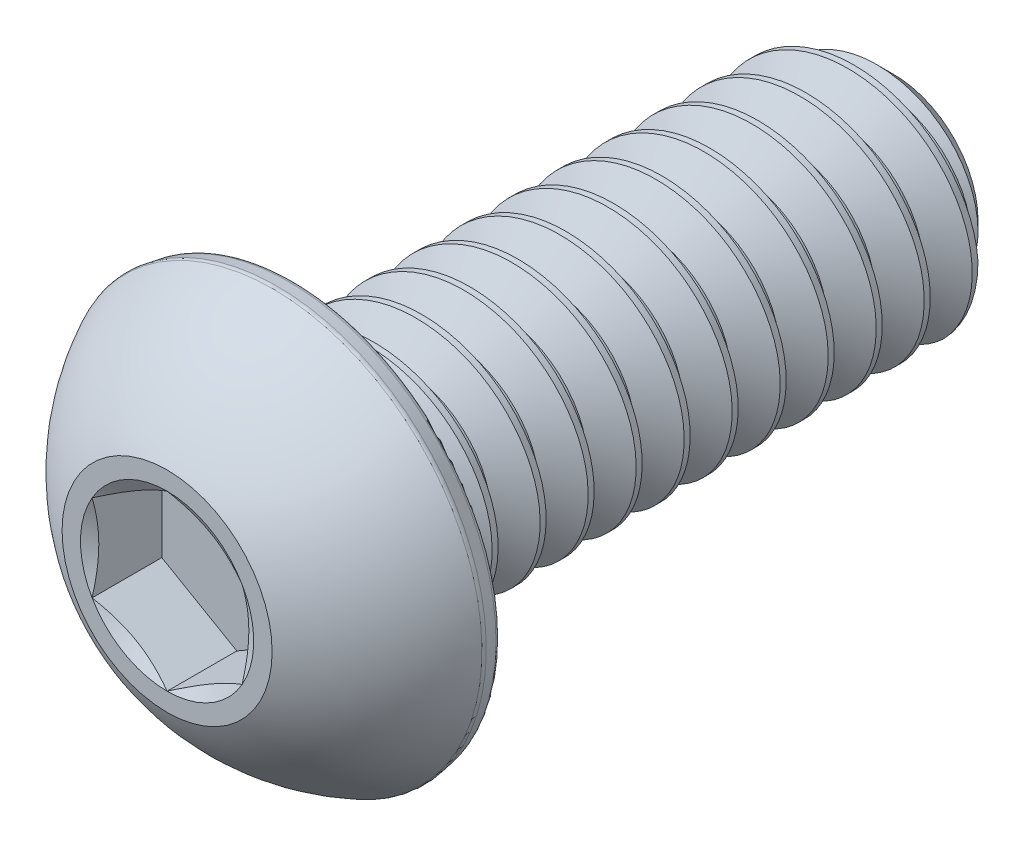
SolidWorks part; units mm, degrees
ref_plane "Front Plane" through (0, 0, 0) normal (0, 0, 1) x (1, 0, 0)
ref_plane "Top Plane" through (0, 0, 0) normal (0, 1, 0) x (1, 0, 0)
ref_plane "Right Plane" through (0, 0, 0) normal (1, 0, 0) x (0, 0, -1)
sketch "Sketch1" plane through (0, 0, 0) normal (1, 0, 0) x (0, 0, -1)
  line L0 (-9.6139, 0) -> (9.6139, 0) construction
  line L1 (-9.6139, 0) -> (-9.6139, 5.5499)
  line L2 (-9.6139, 5.5499) -> (-6.2611, 5.5499)
  line L3 (-6.2611, 5.5499) -> (-6.2611, 3.175)
  line L4 (-6.2611, 3.175) -> (9.6139, 3.175)
  line L5 (9.6139, 3.175) -> (9.6139, 0)
  point P2 (0, 0)
  point P4 (8.3439, 0)
  point P9 (7.7089, 3.175)
  point P10 (7.7089, -3.175)
  point P11 (9.6139, -3.175)
  point P15 (-7.7699, 0)
  dimension "Head Height" = 3.3528
  dimension "Head Diameter" = 11.0998
  dimension "Length" = 15.875
  dimension "Screw Size Decimal Equivalent" = 6.35
  dimension "Thread Pitch" = 1.27
  dimension "D1" = 1.905
  dimension "D2" = 1.844
sketch "Sketch2" plane through (0, 0, 0) normal (0, 0, 1) x (1, 0, 0)
  line L0 (0, 3.175) -> (0, 0) construction
  line L1 (0, 2.2914) -> (-1.9844, 1.1457)
  line L2 (-1.9844, 1.1457) -> (-1.9844, -1.1457)
  line L3 (-1.9844, -1.1457) -> (0, -2.2914)
  line L4 (0, -2.2914) -> (1.9844, -1.1457)
  line L5 (1.9844, -1.1457) -> (1.9844, 1.1457)
  line L6 (1.9844, 1.1457) -> (0, 2.2914)
  circle A0 centre (0, 0) radius 1.9844 construction
  circle A1 centre (0, 0) radius 2.7781
  point P10 (0, 2.7781)
  dimension "D1" = 5.5563
  dimension "Drive Size" = 3.9688
sketch "Sketch3" plane through (0, 0, 0) normal (1, 0, 0) x (0, 0, -1)
  line L0 (-9.6139, 0) -> (-9.6139, 2.7781)
  line L1 (-9.6139, 0) -> (-9.6139, 5.5499) construction
  line L2 (-9.6139, 5.5499) -> (-6.2611, 5.5499) construction
  line L3 (-6.764, 5.5499) -> (-6.2611, 5.4612)
  line L4 (-6.2611, 5.5499) -> (-6.2611, 3.175) construction
  line L5 (-6.2611, 5.4612) -> (-6.2611, 3.175)
  line L6 (-9.6139, 0) -> (9.6139, 0) construction
  line L7 (-9.6139, 0) -> (9.6139, 0)
  line L8 (9.6139, 0) -> (9.6139, 2.2225)
  line L9 (9.6139, 3.175) -> (9.6139, 0) construction
  line L10 (9.6139, 2.2225) -> (8.6614, 3.175)
  line L11 (-6.2611, 3.175) -> (9.6139, 3.175) construction
  line L12 (8.6614, 3.175) -> (-6.2611, 3.175)
  arc A0 (-9.6139, 2.7781) -> (-6.764, 5.5499) centre (-4.1391, 0) cw
  dimension "D1" = 0.5029
  dimension "D2" = 10
  dimension "D3" = 45
  dimension "D4" = 0.9525
revolve "Revolve1" add sketch "Sketch3" angle 360 about L7
sketch "Sketch4" plane through (0, 0, 9.6139) normal (0, 0, 1) x (1, 0, 0)
  line L0 (-1.9844, -1.1457) -> (0, -2.2914) construction
  line L1 (-1.9844, 1.1457) -> (-1.9844, -1.1457) construction
  line L2 (0, 2.2914) -> (-1.9844, 1.1457) construction
  line L3 (1.9844, 1.1457) -> (0, 2.2914) construction
  line L4 (1.9844, -1.1457) -> (1.9844, 1.1457) construction
  line L5 (0, -2.2914) -> (1.9844, -1.1457) construction
  line L6 (-1.9844, -1.1457) -> (0, -2.2914)
  line L7 (-1.9844, 1.1457) -> (-1.9844, -1.1457)
  line L8 (0, 2.2914) -> (-1.9844, 1.1457)
  line L9 (1.9844, 1.1457) -> (0, 2.2914)
  line L10 (1.9844, -1.1457) -> (1.9844, 1.1457)
  line L11 (0, -2.2914) -> (1.9844, -1.1457)
extrude "Cut-Extrude1" cut sketch "Sketch4" against normal up to vertex (1.844 mm away) up to point (0, 0, 7.7699)
sketch "Sketch5" plane through (0, 0, 9.6139) normal (0, 0, 1) x (1, 0, 0)
  circle A0 centre (0, 0) radius 2.2914
extrude "Cut-Extrude2" cut sketch "Sketch5" against normal up to vertex (1.844 mm away) draft 60 up to point (0, 0, 7.7699)
fillet "Fillet1" radius 0.1676 2 edges at (5.5499, 0, 6.764) (5.4612, 0, 6.2611)
split "Split1" bodies to split 106 resulting bodies 107 108 split by face at (5.3206, 0, 6.2611)
sketch "Sketch6" plane through (0, 0, -9.6139) normal (0, 0, -1) x (-1, 0, 0)
  circle A0 centre (0, 0) radius 3.175 construction
  circle A1 centre (0, 0) radius 3.175
curve "Helix/Spiral1" pitch 1.27 height 17.145 radius 3.175 centre (0, 0, -9.6139) axis (0, 0, 1) start towards (0, 1, 0)
sketch "Sketch7" plane through (0, 0, 0) normal (1, 0, 0) x (0, 0, -1)
  line L0 (9.5345, 3.3125) -> (10.1695, 2.2126) construction
  line L1 (10.1695, 2.2126) -> (10.8045, 3.3125) construction
  line L2 (10.8045, 3.3125) -> (9.5345, 3.3125) construction
  line L3 (9.5742, 3.2437) -> (10.7648, 3.2437)
  line L4 (10.7648, 3.2437) -> (10.2489, 2.3501)
  line L5 (10.2489, 2.3501) -> (10.0902, 2.3501)
  line L6 (10.0902, 2.3501) -> (9.5742, 3.2437)
  line L7 (10.1695, 2.3501) -> (10.1695, 2.2126) construction
  line L8 (9.6139, 3.175) -> (10.7252, 3.175) construction
  line L9 (10.1695, 3.3125) -> (10.1695, 3.175) construction
  point P12 (10.1695, 3.2437)
  dimension "D1" = 1.27
  dimension "D2" = 0.1588
sweep "Cut-Sweep1" cut profiles "Sketch7" path "Helix/Spiral1" align with end faces yes
sketch "Sketch8" plane through (0, 0, 6.2611) normal (0, 0, -1) x (-1, 0, 0)
  circle A0 centre (0, 0) radius 3.3125
extrude "Boss-Extrude1" add sketch "Sketch8" along normal up to vertex (13.97 mm away) draft 45 up to point (0, 3.175, -7.7089)
equation "\"D1@Sketch1\"=\"Thread Pitch@Sketch1\"*1.5"
equation "\"D2@Sketch1\"=0.55*\"Head Height@Sketch1\""
equation "\"D1@Sketch2\"=\"Drive Size@Sketch2\"*1.4"
equation "\"D1@Sketch3\"=0.15*\"Head Height@Sketch1\""
equation "\"D4@Sketch3\"=0.75*\"Thread Pitch@Sketch1\""
equation "\"D1@Fillet1\"=.05*\"Head Height@Sketch1\""
equation "\"D4@Helix/Spiral1\"=\"Thread Pitch@Sketch1\""
equation "\"D3@Helix/Spiral1\"=\"Length@Sketch1\"+\"Thread Pitch@Sketch1\""
equation "\"D2@Sketch7\"=\"D1@Sketch7\"/8"
equation "\"D1@Sketch7\"=\"Thread Pitch@Sketch1\""
